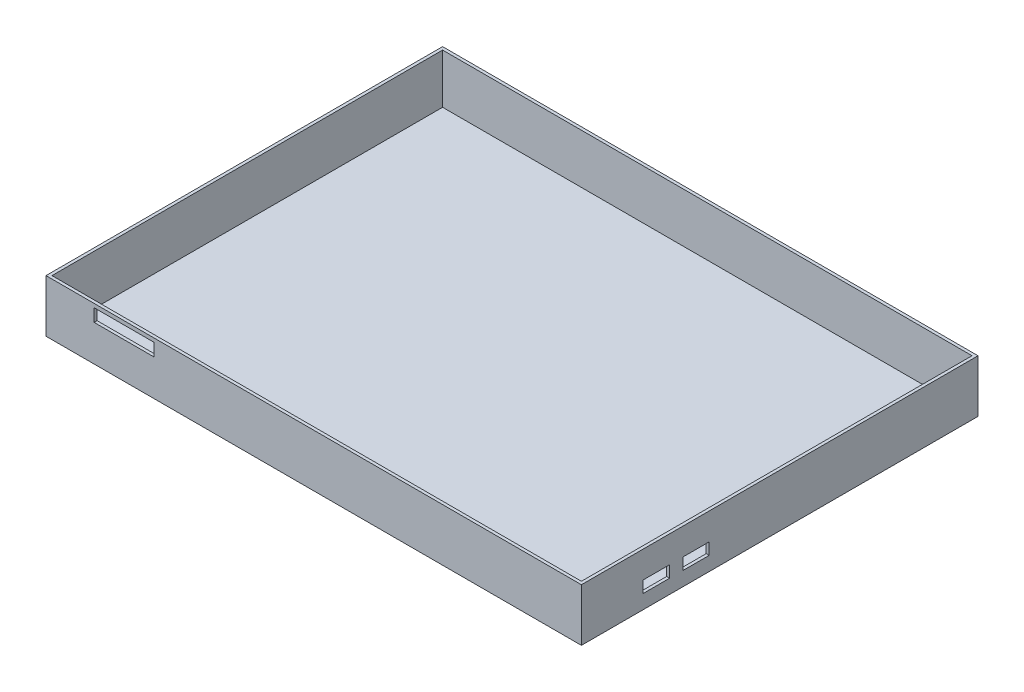
SolidWorks part; units mm, degrees
material "PLA"
ref_plane "Спереди" through (0, 0, 0) normal (0, 0, 1) x (1, 0, 0)
ref_plane "Сверху" through (0, 0, 0) normal (0, 1, 0) x (1, 0, 0)
ref_plane "Справа" through (0, 0, 0) normal (1, 0, 0) x (0, 0, -1)
sketch "Эскиз1" plane through (0, 0, 0) normal (0, 1, 0) x (1, 0, 0)
  line L1 (135, 100) -> (-135, 100)
  line L2 (135, 100) -> (135, -100)
  line L3 (135, -100) -> (-135, -100)
  line L4 (-135, 100) -> (-135, -100)
  line L5 (135, 100) -> (-135, -100) construction
  line L6 (135, -100) -> (-135, 100) construction
  point P0 (0, 0)
  dimension "D1" = 200
  dimension "D2" = 270
extrude "Бобышка-Вытянуть1" add sketch "Эскиз1" along normal blind 1.5
sketch "Эскиз2" plane through (0, 1.5, 0) normal (0, 1, 0) x (1, 0, 0)
  line L0 (133.5, 98.5) -> (-133.5, 98.5)
  line L1 (-133.5, 98.5) -> (-133.5, -98.5)
  line L2 (-133.5, -98.5) -> (-110.7, -98.5)
  line L3 (133.5, -98.5) -> (133.5, 98.5)
  line L4 (-135, 100) -> (-135, -100)
  line L5 (-135, -100) -> (135, -100)
  line L6 (135, -100) -> (135, 100)
  line L7 (135, 100) -> (-135, 100)
  line L8 (-135, 100) -> (-135, -100)
  line L9 (-135, -100) -> (-110.7, -100)
  line L10 (135, -100) -> (135, 100)
  line L11 (135, 100) -> (-135, 100)
  line L12 (-110.7, -98.5) -> (-110.7, -100)
  line L14 (-80.5, -98.5) -> (-80.5, -100)
  line L16 (-80.5, -98.5) -> (133.5, -98.5)
  line L17 (-80.5, -100) -> (135, -100)
  line L18 (-133.5, -98.5) -> (133.5, -98.5) construction
  line L20 (-135, -100) -> (135, -100) construction
  dimension "D3" = 24.3
  dimension "D4" = 54.5
  dimension "D1" = 0
  dimension "D2" = 1.5
extrude "Бобышка-Вытянуть2" add sketch "Эскиз2" along normal offset from surface (25 mm away) 7 offset beyond the face yes
sketch "Эскиз3" plane through (0, 1.5, 0) normal (0, 1, 0) x (1, 0, 0)
  line L1 (-110.7, -98.5) -> (-80.5, -98.5)
  line L2 (-110.7, -98.5) -> (-110.7, -100)
  line L3 (-110.7, -100) -> (-80.5, -100)
  line L4 (-80.5, -98.5) -> (-80.5, -100)
extrude "Бобышка-Вытянуть3" add sketch "Эскиз3" along normal blind 16.7
sketch "Эскиз4" plane through (-110.7, 0, 0) normal (1, 0, 0) x (0, 0, -1)
  line L0 (-100, 26.5) -> (-100, 18.2) construction
  line L1 (-98.5, 26.5) -> (-100, 26.5)
  line L2 (-98.5, 26.5) -> (-98.5, 24.6)
  line L3 (-98.5, 24.6) -> (-100, 24.6)
  line L4 (-100, 26.5) -> (-100, 24.6)
  dimension "D1" = 1.9
extrude "Бобышка-Вытянуть4" add sketch "Эскиз4" along normal up to surface (30.2 mm away) up to face at (-80.5, 22.35, 99.25)
sketch "Эскиз5" plane through (135, 0, 0) normal (1, 0, 0) x (0, 0, -1)
  line L0 (-100, 26.5) -> (-100, 0) construction
  line L1 (-55.55, 13) -> (-68.85, 13)
  line L2 (-55.55, 13) -> (-55.55, 7.1)
  line L3 (-55.55, 7.1) -> (-68.85, 7.1)
  line L4 (-68.85, 13) -> (-68.85, 7.1)
  line L5 (-55.55, 13) -> (-68.85, 7.1) construction
  line L6 (-55.55, 7.1) -> (-68.85, 13) construction
  line L7 (-35.55, 13) -> (-48.85, 13)
  line L8 (-35.55, 13) -> (-35.55, 7.1)
  line L9 (-35.55, 7.1) -> (-48.85, 7.1)
  line L10 (-48.85, 13) -> (-48.85, 7.1)
  line L11 (-35.55, 13) -> (-48.85, 7.1) construction
  line L12 (-35.55, 7.1) -> (-48.85, 13) construction
  line L13 (-100, 0) -> (100, 0) construction
  point P0 (-62.2, 10.05)
  point P5 (-42.2, 10.05)
  dimension "D1" = 13.3
  dimension "D2" = 5.9
  dimension "D3" = 6.7
  dimension "D4" = 31.15
  dimension "D5" = 13
extrude "Вырез-Вытянуть1" cut sketch "Эскиз5" against normal up to surface (1.5 mm away) up to face at (133.5, 14, 0)
